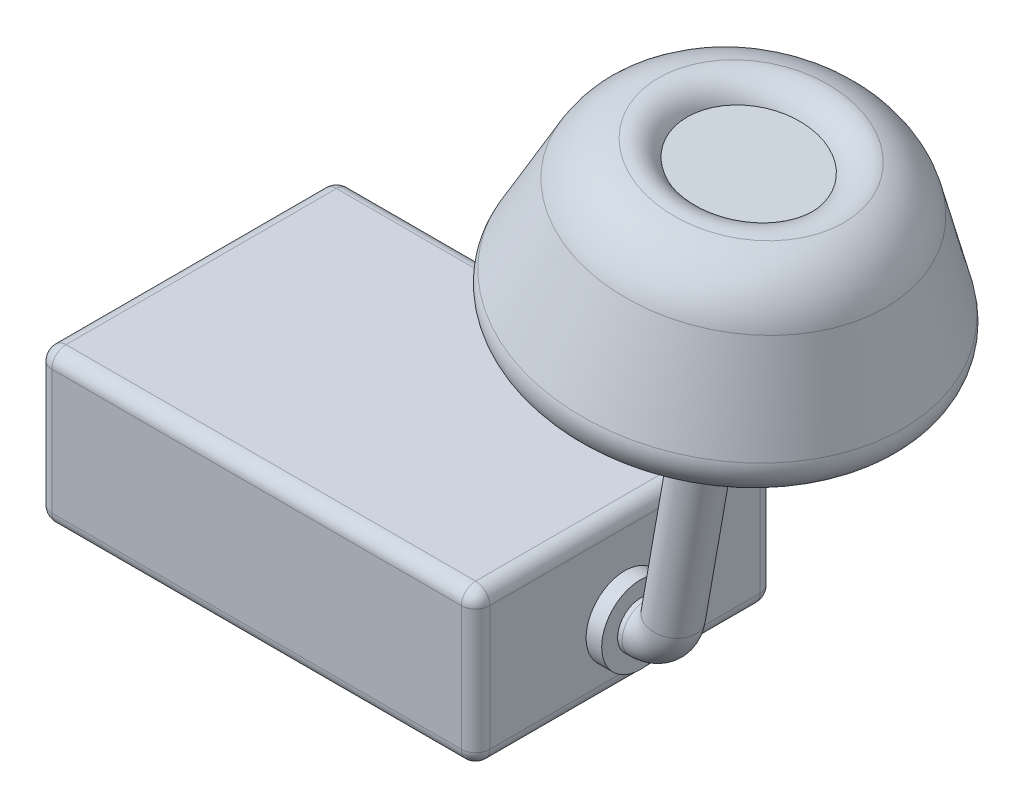
SolidWorks part; units mm, degrees
material "PA Type 6"
ref_plane "Front Plane" through (0, 0, 0) normal (0, 0, 1) x (1, 0, 0)
ref_plane "Top Plane" through (0, 0, 0) normal (0, 1, 0) x (1, 0, 0)
ref_plane "Right Plane" through (0, 0, 0) normal (1, 0, 0) x (0, 0, -1)
sketch "Sketch1" plane through (0, 0, 0) normal (0, 1, 0) x (1, 0, 0)
  line L1 (-19.5834, 13.3604) -> (19.5834, 13.3604)
  line L2 (-19.5834, 13.3604) -> (-19.5834, -13.3604)
  line L3 (-19.5834, -13.3604) -> (19.5834, -13.3604)
  line L4 (19.5834, 13.3604) -> (19.5834, -13.3604)
  point P4 (0, -13.3604)
  point P6 (19.5834, 0)
  dimension "D1" = 39.1668
  dimension "D2" = 26.7208
extrude "Boss-Extrude1" add sketch "Sketch1" along normal blind 13.6652
sketch "Sketch2" plane through (19.5834, 0, 0) normal (1, 0, 0) x (0, 0, -1)
  line L0 (-13.3604, 0) -> (13.3604, 0) construction
  circle A0 centre (0, 5.588) radius 3.4798
  dimension "D1" = 6.9596
  dimension "D2" = 5.588
extrude "Boss-Extrude2" add sketch "Sketch2" along normal blind 1.397
sketch "Sketch3" plane through (0, 0, 0) normal (0, 0, 1) x (1, 0, 0)
  line L0 (20.9804, 5.588) -> (21.3891, 5.588)
  line L2 (20.9804, 2.1082) -> (20.9804, 9.0678) construction
  line L3 (23.8905, 7.6869) -> (26.1668, 20.5965)
  line L4 (26.1668, 20.5965) -> (26.6079, 23.0979)
  arc A0 (23.8905, 7.6869) -> (21.3891, 5.588) centre (21.3891, 8.128) cw
  point P8 (23.5204, 5.588)
  dimension "D2" = 15.24
  dimension "D5" = 2.54
  dimension "D1" = 2.54
  dimension "D3" = 80
  dimension "D4" = 2.54
sketch "Sketch4" plane through (20.9804, 0, 0) normal (1, 0, 0) x (0, 0, -1)
  circle A2 centre (0, 5.588) radius 2.0574
  dimension "D1" = 4.1148
sweep "Sweep1" add profiles "Sketch4" path "Sketch3"
sketch "Sketch5" plane through (4.7523, 26.9516, 0) normal (0.1736, 0.9848, 0) x (0.9848, -0.1736, 0)
  circle A0 centre (22.1927, 0) radius 3.4036
  dimension "D1" = 6.8072
extrude "Boss-Extrude3" add sketch "Sketch5" along normal blind 8.89
sketch "Sketch6" plane through (6.296, 35.7065, 0) normal (0.1736, 0.9848, 0) x (0.9848, -0.1736, 0)
  circle A0 centre (22.1927, 0) radius 17.145
  dimension "D1" = 34.29
extrude "Boss-Extrude4" add sketch "Sketch6" along normal blind 15.8242 draft 20
sketch "Sketch7" plane through (9.0439, 51.2903, 0) normal (0.1736, 0.9848, 0) x (0.9848, -0.1736, 0)
  circle A0 centre (22.1927, 0) radius 5.588
  dimension "D1" = 11.176
extrude "Cut-Extrude1" cut sketch "Sketch7" against normal blind 1.4478
fillet "Fillet1" radius 2.54 2 edges at (11.2671, 34.83, 0) (24.7997, 32.4439, 0)
fillet "Fillet2" radius 6.35 1 edges at (19.6869, 49.4137, 0)
fillet "Fillet3" radius 2.54 1 edges at (25.3963, 48.407, 0)
fillet "Fillet4" radius 1.27 12 edges at (-19.5834, 0, 0) (0, 0, 13.3604) (19.5834, 0, 0) (0, 0, -13.3604) (-19.5834, 13.6652, 0) (19.5834, 13.6652, 0) (0, 13.6652, -13.3604) (-19.5834, 6.8326, -13.3604) (19.5834, 6.8326, -13.3604) (19.5834, 6.8326, 13.3604) (-19.5834, 6.8326, 13.3604) (0, 13.6652, 13.3604)
